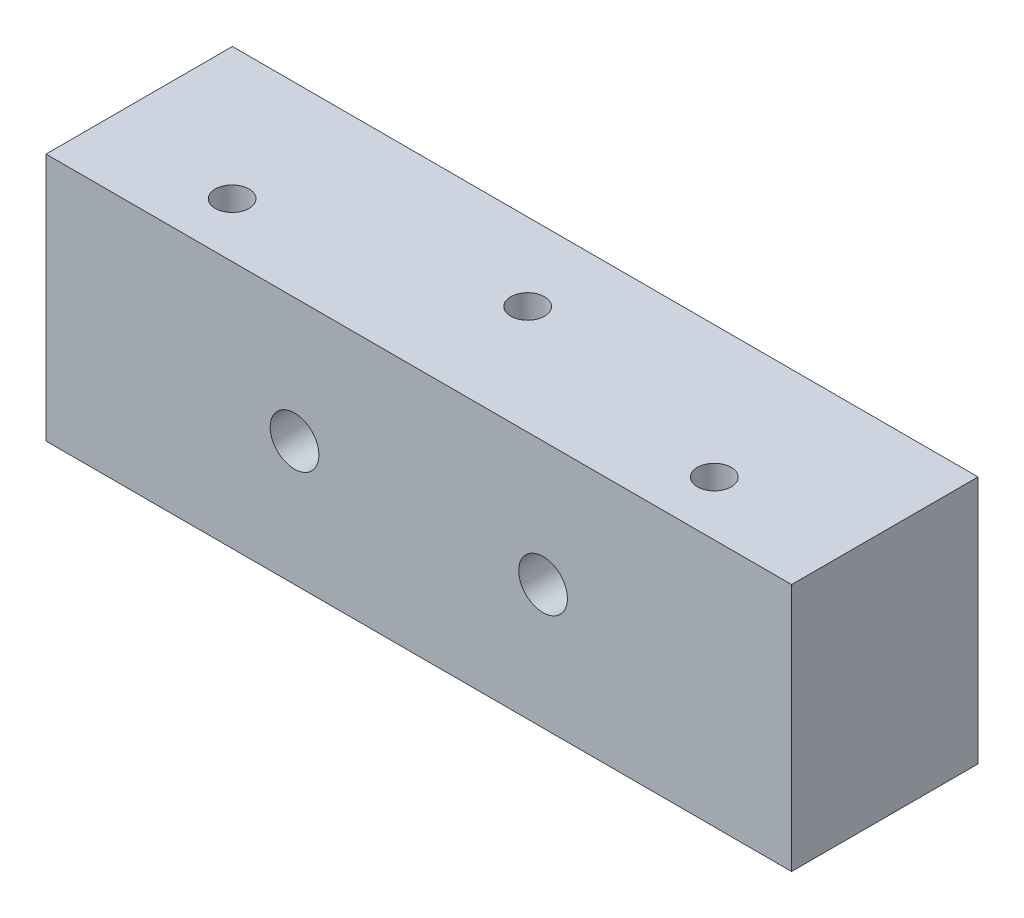
SolidWorks part; units mm, degrees
material "ABS"
ref_plane "Front Plane" through (0, 0, 0) normal (0, 0, 1) x (1, 0, 0)
ref_plane "Top Plane" through (0, 0, 0) normal (0, 1, 0) x (1, 0, 0)
ref_plane "Right Plane" through (0, 0, 0) normal (1, 0, 0) x (0, 0, -1)
sketch "Sketch1" plane through (0, 0, 0) normal (0, 1, 0) x (1, 0, 0)
  line L1 (-38.1, -9.525) -> (38.1, -9.525)
  line L2 (-38.1, -9.525) -> (-38.1, 9.525)
  line L3 (-38.1, 9.525) -> (38.1, 9.525)
  line L4 (38.1, -9.525) -> (38.1, 9.525)
  line L5 (-38.1, -9.525) -> (38.1, 9.525) construction
  line L6 (-38.1, 9.525) -> (38.1, -9.525) construction
  point P0 (0, 0)
  dimension "D1" = 19.05
  dimension "D2" = 76.2
extrude "Boss-Extrude1" add sketch "Sketch1" along normal mid plane 25.4
sketch "Sketch2" plane through (0, -12.7, 0) normal (0, -1, 0) x (1, 0, 0)
  circle A1 centre (0, -1.6002) radius 4.1656 construction
  circle A2 centre (24.638, 3.9624) radius 4.1656 construction
  circle A3 centre (-24.638, 3.9624) radius 4.1656 construction
  circle A4 centre (0, -1.6002) radius 4.1656
  circle A5 centre (24.638, 3.9624) radius 4.1656
  circle A6 centre (-24.638, 3.9624) radius 4.1656
hole_wizard "#8-32 Tapped Hole1" positions "3DSketch1" profile "Sketch4" tap size "#8-32" standard "ANSI Inch" end condition through all
sketch3d "3DSketch1"
  point P0 (-24.638, -12.7, 3.9624)
  point P2 (0, -12.7, -1.6002)
  point P5 (24.638, -12.7, 3.9624)
sketch "Sketch4" plane through (-24.638, -12.7, 3.9624) normal (1, 0, 0) x (0, 0, -1)
  line L0 (0, 0) -> (0, 25.4)
  line L1 (0, 25.4) -> (1.7272, 25.4)
  line L2 (1.7272, 25.4) -> (1.7272, 0)
  line L5 (1.7272, 0) -> (0, 0)
  line L11 (0, -6.35) -> (0, 107.95) construction
  dimension "Thru Tap Drill Dia." = 3.4544
  dimension "Thru Tap Drill Depth" = 25.4
cosmetic thread "Hole Thread1" parameters "D2"=4.1656
cosmetic thread "Hole Thread2" parameters "D2"=4.1656
cosmetic thread "Hole Thread3" parameters "D2"=4.1656
hole_wizard "#10 Clearance Hole1" positions "Sketch6" profile "Sketch8" hole size "#10" standard "ANSI Inch" end condition through all
sketch "Sketch6" plane through (0, 0, -9.525) normal (0, 0, -1) x (-1, 0, 0)
  line L0 (-12.7, 0) -> (12.7, 0)
  point P0 (-12.7, 0)
  point P2 (12.7, 0)
  dimension "D1" = 25.4
sketch "Sketch8" plane through (12.7, 0, -9.525) normal (1, 0, 0) x (0, 1, 0)
  line L0 (0, 0) -> (0, 19.05)
  line L1 (0, 19.05) -> (2.4892, 19.05)
  line L2 (2.4892, 19.05) -> (2.4892, 0)
  line L5 (2.4892, 0) -> (0, 0)
  line L11 (0, -6.35) -> (0, 107.95) construction
  dimension "Thru Hole Dia." = 4.9784
  dimension "Thru Hole Depth" = 19.05
